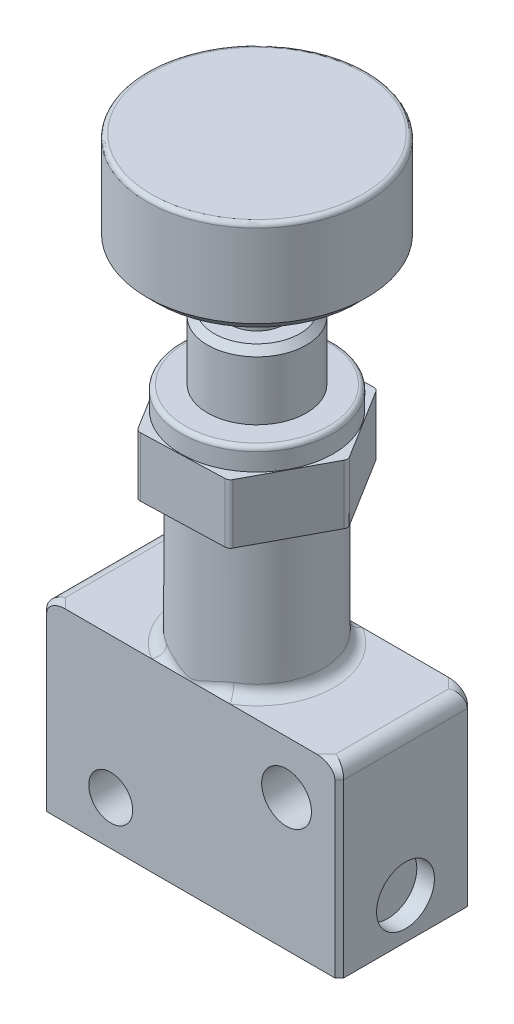
SolidWorks part; units mm, degrees
ref_plane "Front Plane" through (0, 0, 0) normal (0, 0, 1) x (1, 0, 0)
ref_plane "Top Plane" through (0, 0, 0) normal (0, 1, 0) x (1, 0, 0)
ref_plane "Right Plane" through (0, 0, 0) normal (1, 0, 0) x (0, 0, -1)
sketch "Sketch1" plane through (0, 0, 0) normal (0, 1, 0) x (1, 0, 0)
  line L1 (0, 0) -> (42.9006, 0)
  line L2 (0, 0) -> (0, 19.1262)
  line L3 (0, 19.1262) -> (42.9006, 19.1262)
  line L4 (42.9006, 0) -> (42.9006, 19.1262)
  dimension "D1" = 42.9006
  dimension "D2" = 19.1262
extrude "Boss-Extrude1" add sketch "Sketch1" along normal blind 26.6954
sketch "Sketch2" plane through (0, 26.6954, 0) normal (0, 1, 0) x (1, 0, 0)
  circle A0 centre (21.4503, 9.5631) radius 9.525
  dimension "D1" = 19.05
extrude "Boss-Extrude2" add sketch "Sketch2" along normal blind 49.7332
sketch "Sketch3" plane through (0, 76.4286, 0) normal (0, 1, 0) x (1, 0, 0)
  circle A0 centre (21.4503, 9.5631) radius 15.8877
  dimension "D1" = 31.7754
extrude "Boss-Extrude3" add sketch "Sketch3" along normal blind 14.0462
sketch "Sketch4" plane through (0, 0, 0) normal (0, 0, 1) x (1, 0, 0)
  line L1 (42.9006, 26.6954) -> (35.2806, 26.6954)
  line L2 (42.9006, 26.6954) -> (42.9006, 19.0754)
  line L3 (42.9006, 19.0754) -> (35.2806, 19.0754)
  line L4 (35.2806, 26.6954) -> (35.2806, 19.0754)
  line L5 (35.2806, 19.0754) -> (9.8806, 19.0754)
  line L6 (35.2806, 19.0754) -> (35.2806, 6.3754)
  line L7 (35.2806, 6.3754) -> (9.8806, 6.3754)
  line L8 (9.8806, 19.0754) -> (9.8806, 6.3754)
  circle A0 centre (35.2806, 19.0754) radius 3.5941
  circle A1 centre (9.8806, 6.3754) radius 3.175
  dimension "D3" = 7.1882
  dimension "D6" = 6.35
  dimension "D1" = 7.62
  dimension "D2" = 7.62
  dimension "D4" = 12.7
  dimension "D5" = 25.4
extrude "Cut-Extrude1" cut sketch "Sketch4" against normal blind 25.4 contours L6 A0 L3 | L3 A0 L4 | L4 A0 L5 | L5 A0 L6 | L7 A1 L8 | L8 A1 L7
sketch "Sketch5" plane through (0, 0, -19.1262) normal (0, 0, -1) x (-1, 0, 0)
  circle A0 centre (-35.2806, 19.0754) radius 5.207
  circle A1 centre (-9.8806, 6.3754) radius 5.0482
  dimension "D1" = 10.414
  dimension "D2" = 10.0965
extrude "Cut-Extrude2" cut sketch "Sketch5" against normal blind 7.112
sketch "Sketch6" plane through (0, 76.4286, 0) normal (0, -1, 0) x (1, 0, 0)
  circle A0 centre (21.4503, -9.5631) radius 3.9116
  circle A1 centre (21.4503, -9.5631) radius 9.525
  dimension "D1" = 7.8232
extrude "Cut-Extrude3" cut sketch "Sketch6" along normal blind 7.9248
sketch "Sketch7" plane through (0, 68.5038, 0) normal (0, 1, 0) x (1, 0, 0)
  circle A1 centre (21.4503, 9.5631) radius 7.1374
  circle A2 centre (21.4503, 9.5631) radius 9.525
  dimension "D1" = 14.2748
extrude "Cut-Extrude4" cut sketch "Sketch7" against normal blind 9.4488
sketch "Sketch9" plane through (0, 59.055, 0) normal (0, 1, 0) x (1, 0, 0)
  circle A0 centre (21.4503, 9.5631) radius 11.0109
  dimension "D1" = 22.0218
extrude "Boss-Extrude5" add sketch "Sketch9" against normal blind 3.175
sketch "Sketch10" plane through (0, 55.88, 0) normal (0, -1, 0) x (1, 0, 0)
  line L1 (34.2459, -9.9752) -> (28.205, 1.3122)
  line L2 (28.205, 1.3122) -> (15.4094, 1.7243)
  line L3 (15.4094, 1.7243) -> (8.6547, -9.151)
  line L4 (8.6547, -9.151) -> (14.6956, -20.4384)
  line L5 (14.6956, -20.4384) -> (27.4912, -20.8505)
  line L6 (27.4912, -20.8505) -> (34.2459, -9.9752)
  circle A0 centre (21.4503, -9.5631) radius 11.0871 construction
  dimension "D1" = 22.1742
extrude "Boss-Extrude6" add sketch "Sketch10" along normal blind 8.5725
sketch "Sketch8" plane through (0, 0, 0) normal (-1, 0, 0) x (0, 0, 1)
  line L0 (-9.5631, 0) -> (-9.5631, 11.9126)
  line L1 (-19.1262, 0) -> (0, 0) construction
  line L2 (-9.5631, 26.6954) -> (-9.5631, 19.9771)
  line L4 (-19.1262, 26.6954) -> (0, 26.6954) construction
  circle A0 centre (-9.5631, 16.0909) radius 4.1783
  dimension "D2" = 8.3566
  dimension "D1" = 11.9126
  dimension "D3" = 6.7183
extrude "Cut-Extrude5" cut sketch "Sketch8" against normal blind 2.54
sketch "Sketch11" plane through (42.9006, 0, 0) normal (1, 0, 0) x (0, 0, -1)
  line L0 (9.5631, 26.6954) -> (9.5631, 10.0584)
  line L1 (0, 26.6954) -> (19.1262, 26.6954) construction
  circle A0 centre (9.5631, 5.8801) radius 4.1783
  dimension "D2" = 8.3566
  dimension "D1" = 16.637
extrude "Cut-Extrude6" cut sketch "Sketch11" against normal blind 2.54 contours A0
chamfer "Chamfer1" distance 1.4605 angle 45 1 edges at (21.4503, 76.4286, 6.3246)
chamfer "Chamfer2" distance 0.9525 angle 45 1 edges at (21.4503, 68.5038, -2.4257)
chamfer "Chamfer3" distance 0.635 angle 45 4 edges at (0, 13.3477, -19.1262) (42.9006, 13.3477, -19.1262) (42.9006, 13.3477, 0) (0, 13.3477, 0)
fillet "Fillet1" radius 0.635 1 edges at (21.4503, 90.4748, 6.3246)
fillet "Fillet2" radius 0.635 1 edges at (21.4503, 59.055, 1.4478)
fillet "Fillet3" radius 1.905 6 edges at (42.9006, 26.6954, -9.5631) (0, 26.6954, -9.5631) (0.3175, 26.6954, -18.8087) (0.3175, 26.6954, -0.3175) (42.5831, 26.6954, -0.3175) (42.5831, 26.6954, -18.8087)
fillet "Fillet4" radius 1.5875 1 edges at (21.4503, 26.6954, -0.0381)
fillet "Fillet5" radius 0.7937 6 edges at (27.4912, 51.5938, -20.8505) (14.6956, 51.5938, -20.4384) (8.6547, 51.5938, -9.151) (28.205, 51.5938, 1.3122) (34.2459, 51.5938, -9.9752) (15.4094, 51.5938, 1.7243)
